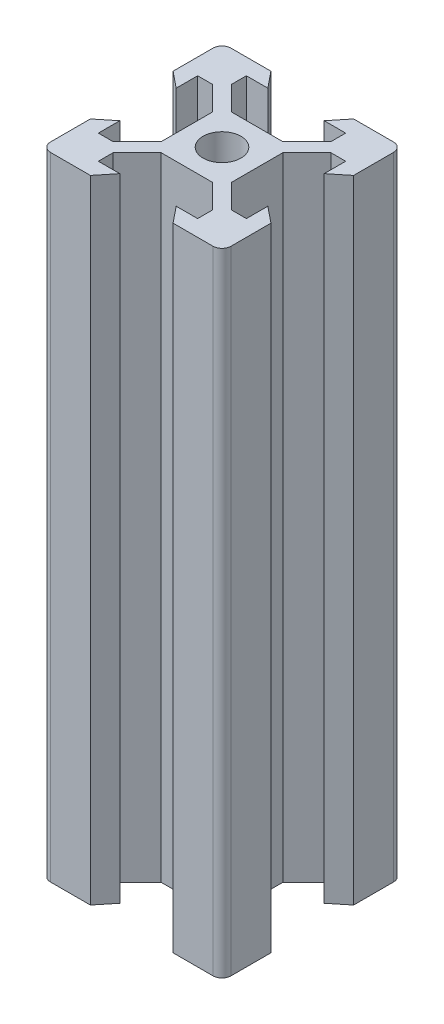
SolidWorks part; units mm, degrees
ref_plane "Front Plane" through (0, 0, 0) normal (0, 0, 1) x (1, 0, 0)
ref_plane "Top Plane" through (0, 0, 0) normal (0, 1, 0) x (1, 0, 0)
ref_plane "Right Plane" through (0, 0, 0) normal (1, 0, 0) x (0, 0, -1)
sketch "Sketch1" plane through (0, 0, 0) normal (0, 1, 0) x (1, 0, 0)
  line L0 (-3.125, 8.2) -> (-4.58, 10)
  line L1 (-9, 10) -> (9, 10)
  line L2 (-10, 9) -> (-10, -9)
  line L3 (-9, -10) -> (9, -10)
  line L4 (10, 9) -> (10, -9)
  line L5 (-10, 10) -> (10, -10) construction
  line L6 (-10, -10) -> (10, 10) construction
  line L7 (-10, 0) -> (0, 0) construction
  line L8 (0, 10) -> (0, 0) construction
  line L9 (-8.2, 3.125) -> (-10, 4.58)
  line L10 (-8.2, 3.125) -> (-8.2, 5.5)
  line L11 (-3.125, 8.2) -> (-5.5, 8.2)
  line L12 (-5.5, 8.2) -> (-5.5, 6.56)
  line L13 (-2.84, 3.9) -> (2.84, 3.9)
  line L14 (-5.5, 6.56) -> (-2.84, 3.9)
  line L15 (-8.2, 5.5) -> (-6.56, 5.5)
  line L16 (-6.56, 5.5) -> (-3.9, 2.84)
  line L17 (-3.9, 2.84) -> (-3.9, -2.84)
  line L18 (3.9, 2.84) -> (3.9, -2.84)
  line L19 (6.56, 5.5) -> (3.9, 2.84)
  line L20 (8.2, 5.5) -> (6.56, 5.5)
  line L21 (8.2, 3.125) -> (8.2, 5.5)
  line L22 (8.2, 3.125) -> (10, 4.58)
  line L23 (3.125, 8.2) -> (4.58, 10)
  line L24 (3.125, 8.2) -> (5.5, 8.2)
  line L25 (5.5, 8.2) -> (5.5, 6.56)
  line L26 (5.5, 6.56) -> (2.84, 3.9)
  line L27 (-8.2, -3.125) -> (-10, -4.58)
  line L28 (-8.2, -3.125) -> (-8.2, -5.5)
  line L29 (-8.2, -5.5) -> (-6.56, -5.5)
  line L30 (-6.56, -5.5) -> (-3.9, -2.84)
  line L31 (8.2, -3.125) -> (10, -4.58)
  line L32 (8.2, -3.125) -> (8.2, -5.5)
  line L33 (8.2, -5.5) -> (6.56, -5.5)
  line L34 (6.56, -5.5) -> (3.9, -2.84)
  line L35 (5.5, -6.56) -> (2.84, -3.9)
  line L36 (5.5, -8.2) -> (5.5, -6.56)
  line L37 (3.125, -8.2) -> (5.5, -8.2)
  line L38 (3.125, -8.2) -> (4.58, -10)
  line L39 (-5.5, -6.56) -> (-2.84, -3.9)
  line L40 (-2.84, -3.9) -> (2.84, -3.9)
  line L41 (-5.5, -8.2) -> (-5.5, -6.56)
  line L42 (-3.125, -8.2) -> (-5.5, -8.2)
  line L43 (-3.125, -8.2) -> (-4.58, -10)
  circle A0 centre (0, 0) radius 2.1
  arc A1 (-10, -9) -> (-9, -10) centre (-9, -9) ccw
  arc A2 (9, -10) -> (10, -9) centre (9, -9) ccw
  arc A3 (9, 10) -> (10, 9) centre (9, 9) cw
  arc A4 (-9, 10) -> (-10, 9) centre (-9, 9) ccw
  point P0 (0, 0)
  point P35 (0, 3.9)
  point P40 (-3.9, 0)
  point P41 (3.9, 0)
  dimension "D3" = 4.2
  dimension "D2" = 1
  dimension "D1" = 20
  dimension "D4" = 6.1
  dimension "D5" = 6.25
  dimension "D6" = 11
  dimension "D7" = 5.68
  dimension "D8" = 9.16
  dimension "D9" = 1.8
extrude "Boss-Extrude1" add sketch "Sketch1" along normal blind 70 contours L43 L42 L41 L39 L40 L35 L36 L37 L38 L3 L4 L31 L32 L33 L34 L18 L19 L20 L21 L22 L1 L23 L24 L25 L26 L13 L14 L12 L11 L0 L2 L9 L10 L15 L16 L17 L30 L29 L28 L27 A0 region at (-4.3125, 0, -8.4828)
